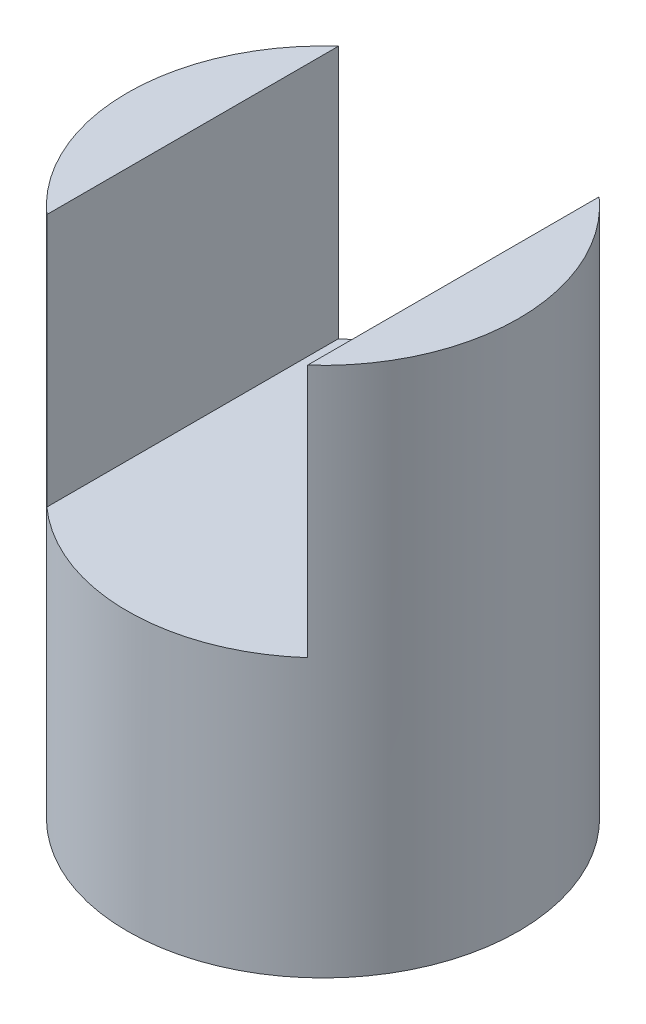
SolidWorks part; units mm, degrees
ref_plane "Front Plane" through (0, 0, 0) normal (0, 0, 1) x (1, 0, 0)
ref_plane "Top Plane" through (0, 0, 0) normal (0, 1, 0) x (1, 0, 0)
ref_plane "Right Plane" through (0, 0, 0) normal (1, 0, 0) x (0, 0, -1)
sketch "Sketch1" plane through (0, 0, 0) normal (0, 1, 0) x (1, 0, 0)
  circle A0 centre (0, 0) radius 9.525
  dimension "D1" = 19.05
extrude "Boss-Extrude1" add sketch "Sketch1" along normal blind 12.5
sketch "Sketch2" plane through (0, 12.5, 0) normal (0, 1, 0) x (1, 0, 0)
  circle A0 centre (0, 0) radius 3
  dimension "D1" = 6
extrude "Cut-Extrude1" cut sketch "Sketch2" against normal up to next
sketch "Sketch3" plane through (0, 12.5, 0) normal (0, 1, 0) x (1, 0, 0)
  circle A0 centre (0, 0) radius 9.525
  dimension "D1" = 19.05
extrude "Boss-Extrude2" add sketch "Sketch3" along normal blind 13.3375
sketch "Sketch4" plane through (0, 0, 0) normal (0, 0, 1) x (1, 0, 0)
  line L0 (9.525, 25.8375) -> (-9.525, 25.8375) construction
  line L1 (-6.35, 13.5) -> (6.35, 13.5)
  line L2 (-6.35, 13.5) -> (-6.35, 25.8375)
  line L3 (-6.35, 25.8375) -> (6.35, 25.8375)
  line L4 (6.35, 13.5) -> (6.35, 25.8375)
  line L5 (-9.525, 25.8375) -> (-9.525, 0) construction
  dimension "D1" = 12.3375
  dimension "D2" = 12.7
  dimension "D3" = 3.175
extrude "Cut-Extrude2" cut sketch "Sketch4" against normal blind 13.3375 and the other way blind 13.3375 contours L1 L4 L3 L2
sketch "Sketch5" plane through (0, 0, 0) normal (0, 0, 1) x (1, 0, 0)
  line L1 (6.35, 13.5) -> (-6.35, 13.5) construction
  circle A0 centre (0, 9.944) radius 2.413
  point P2 (0, 13.5)
  dimension "D3" = 4.826
  dimension "D1" = 0
  dimension "D2" = 3.556
extrude "Cut-Extrude4" cut sketch "Sketch5" against normal blind 13.3375 contours A0
